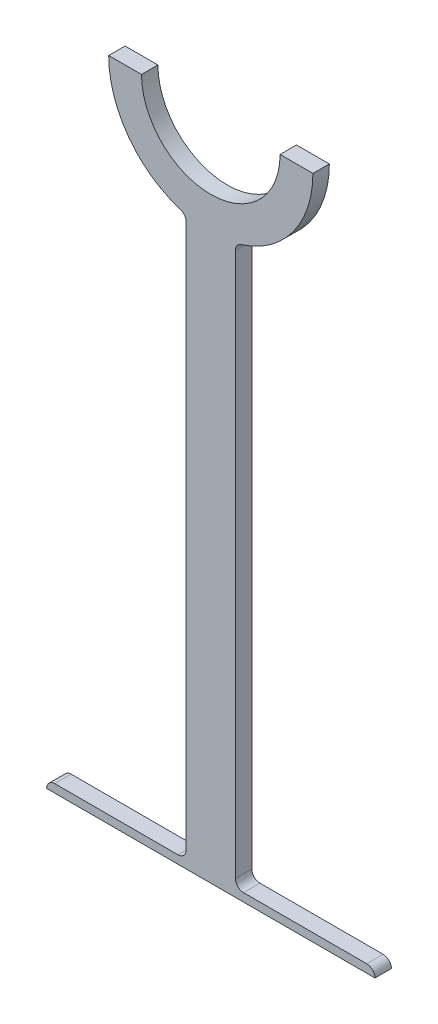
SolidWorks part; units mm, degrees
ref_plane "Front Plane" through (0, 0, 0) normal (0, 0, 1) x (1, 0, 0)
ref_plane "Top Plane" through (0, 0, 0) normal (0, 1, 0) x (1, 0, 0)
ref_plane "Right Plane" through (0, 0, 0) normal (1, 0, 0) x (0, 0, -1)
sketch "Sketch1" plane through (0, 0, 0) normal (0, 0, 1) x (1, 0, 0)
  line L0 (-21.1, 0) -> (-31.1, 0)
  line L1 (21.1, 0) -> (31.1, 0)
  arc A0 (-21.1, 0) -> (21.1, 0) centre (0, 0) ccw
  arc A1 (-31.1, 0) -> (31.1, 0) centre (0, 0) ccw
  dimension "D1" = 21.1
  dimension "D2" = 10
extrude "Boss-Extrude1" add sketch "Sketch1" along normal mid plane 5
sketch "Sketch3" plane through (0, 0, 0) normal (0, 0, 1) x (1, 0, 0)
  line L1 (-7.5, -202.7392) -> (7.5, -202.7392)
  line L2 (-7.5, -202.7392) -> (-7.5, -27.7392)
  line L3 (-7.5, -27.7392) -> (7.5, -27.7392)
  line L4 (7.5, -202.7392) -> (7.5, -27.7392)
  line L5 (-7.5, -202.7392) -> (7.5, -27.7392) construction
  line L6 (-7.5, -27.7392) -> (7.5, -202.7392) construction
  point P0 (0, -115.2392)
  point P5 (0, -202.7392)
  point P8 (0, 0)
  dimension "D1" = 175
  dimension "D2" = 15
extrude "Boss-Extrude2" add sketch "Sketch3" along normal mid plane 5
sketch "Sketch5" plane through (0, 0, 0) normal (1, 0, 0) x (0, 0, -1)
  line L0 (2.5, -202.7392) -> (2.5, -30.1821) construction
  line L1 (-2.5, -202.7392) -> (2.5, -202.7392)
  line L2 (-2.5, -202.7392) -> (-2.5, -200.2392)
  line L3 (-2.5, -200.2392) -> (2.5, -200.2392)
  line L4 (2.5, -202.7392) -> (2.5, -200.2392)
  dimension "D1" = 2.5
extrude "Boss-Extrude4" add sketch "Sketch5" along normal blind 50 and the other way blind 50
fillet "Fillet1" radius 2.5 1 edges at (7.5, -200.2392, 0)
fillet "Fillet2" radius 2.5 1 edges at (-7.5, -200.2392, 0)
fillet "Fillet3" radius 2.5 1 edges at (7.5, -30.1821, 0)
fillet "Fillet4" radius 2.5 1 edges at (-7.5, -30.1821, 0)
fillet "Fillet5" radius 2.5 1 edges at (50, -200.2392, 0)
fillet "Fillet6" radius 2.5 1 edges at (-50, -200.2392, 0)
